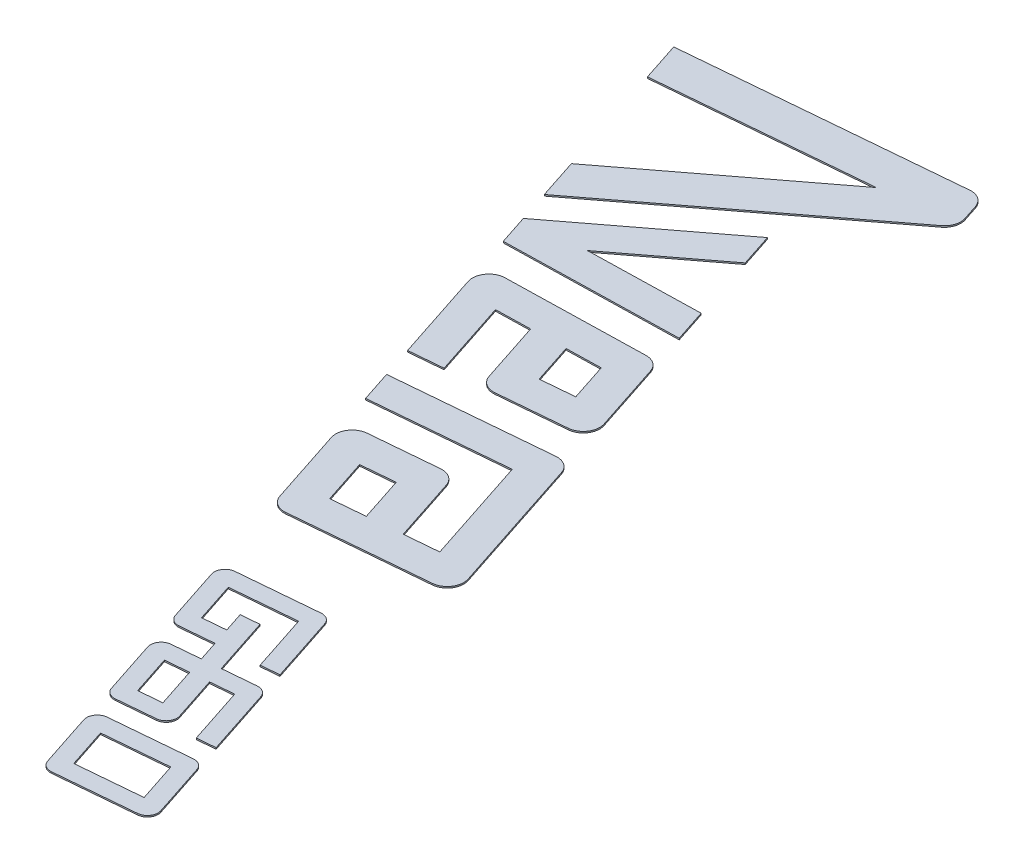
SolidWorks part; units mm, degrees
ref_plane "Front Plane" through (0, 0, 0) normal (0, 0, 1) x (1, 0, 0)
ref_plane "Top Plane" through (0, 0, 0) normal (0, 1, 0) x (1, 0, 0)
ref_plane "Right Plane" through (0, 0, 0) normal (1, 0, 0) x (0, 0, -1)
sketch "Sketch1" plane through (0, 0, 0) normal (0, 1, 0) x (1, 0, 0)
  line L0 (6.2636, 13.3847) -> (6.9802, 11.1991) construction
  line L2 (6.9802, 11.1991) -> (16.6844, 18.5822)
  line L4 (6.9802, 11.1991) -> (7.6656, 9.1086)
  line L5 (19.6969, 9.3941) -> (20.4135, 7.2086) construction
  line L6 (7.6656, 9.1086) -> (19.6969, 9.3941)
  line L10 (7.6656, 9.1086) -> (8.3822, 6.9231) construction
  line L11 (19.5596, 7.1883) -> (9.93, 6.9598)
  line L15 (19.6969, 9.3941) -> (18.9484, 11.677)
  line L20 (11.1641, 11.4923) -> (18.9484, 11.677)
  line L21 (11.1641, 11.4923) -> (17.4428, 16.2692)
  line L26 (11.5324, 4.6972) -> (13.2849, -0.6478)
  line L27 (17.4428, 16.2692) -> (16.6844, 18.5822)
  line L32 (13.0803, 4.7339) -> (11.5324, 4.6972)
  line L39 (5.3404, 16.2005) -> (2.7423, 24.1247) construction
  line L45 (17.2762, 2.0125) -> (16.3584, 4.8117)
  line L46 (13.2849, -0.6478) -> (10.9324, -0.855)
  line L56 (13.0821, -7.4116) -> (20.1616, -6.7881) construction
  line L58 (6.2636, 13.3847) -> (5.3404, 16.2005)
  line L59 (17.4595, 25.4208) -> (5.3404, 16.2005)
  line L60 (13.0821, -7.4116) -> (15.5745, -15.0134) construction
  line L61 (15.5745, -15.0134) -> (27.3591, -13.9756) construction
  line L62 (20.4135, 7.2086) -> (8.3822, 6.9231) construction
  line L64 (20.4135, 7.2086) -> (22.717, 0.1828) construction
  line L65 (8.8645, 5.4519) -> (10.9324, -0.855)
  line L66 (18.7602, 4.8687) -> (16.3584, 4.8117)
  line L68 (20.6796, 6.3969) -> (22.2656, 1.5595)
  line L69 (14.2003, 3.9425) -> (15.3531, 0.4267)
  line L71 (18.7602, 4.8687) -> (19.6287, 2.2197)
  line L72 (19.6287, 2.2197) -> (17.2762, 2.0125)
  line L73 (21.2738, 0.0557) -> (16.5467, -0.3606)
  line L74 (22.717, 0.1828) -> (10.9324, -0.855) construction
  line L75 (18.7602, 4.8687) -> (8.4367, 4.6237) construction
  line L76 (11.6489, -3.0405) -> (12.3655, -5.2261)
  line L77 (19.6287, 2.2197) -> (10.7306, 1.4361) construction
  line L78 (10.9324, -0.855) -> (11.6489, -3.0405) construction
  line L79 (11.6489, -3.0405) -> (22.5243, -2.0828)
  line L80 (12.3655, -5.2261) -> (21.7976, -4.3954)
  line L81 (23.718, -2.8701) -> (26.9077, -12.5989)
  line L82 (21.7976, -4.3954) -> (24.2708, -11.9387)
  line L83 (12.3655, -5.2261) -> (13.0821, -7.4116) construction
  line L84 (20.446, -7.6555) -> (21.9183, -12.1459)
  line L85 (14.5253, -7.2845) -> (19.2524, -6.8682)
  line L86 (13.5335, -8.7884) -> (15.2901, -14.1461)
  line L87 (16.4837, -14.9334) -> (25.9159, -14.1027)
  line L88 (21.2481, -2.7193) -> (25.1736, -14.6922) construction
  line L89 (17.1912, -12.5622) -> (19.5438, -12.355)
  line L90 (23.4336, -2.0027) -> (27.3591, -13.9756) construction
  line L91 (15.3727, -12.7223) -> (27.1574, -11.6845) construction
  line L92 (16.1704, -9.4485) -> (17.1912, -12.5622)
  line L93 (16.1704, -9.4485) -> (18.5229, -9.2414)
  line L95 (16.1704, -9.4485) -> (17.76, -14.2969) construction
  line L96 (18.5449, -9.2394) -> (19.7327, -12.8624) construction
  line L97 (21.9183, -12.1459) -> (24.2708, -11.9387)
  line L98 (1.8466, 26.8566) -> (2.7423, 24.1247)
  line L99 (16.1704, -9.4485) -> (18.5449, -9.2394) construction
  line L100 (18.5229, -9.2414) -> (19.5438, -12.355)
  line L101 (20.1616, -6.7881) -> (21.9183, -12.1459) construction
  line L102 (14.2003, 3.9425) -> (13.9342, 4.7542)
  line L103 (13.0803, 4.7339) -> (13.9342, 4.7542)
  line L104 (15.2901, -14.1461) -> (17.3311, -20.3712) construction
  line L105 (17.4595, 25.4208) -> (2.7423, 24.1247)
  line L106 (22.4342, 26.6593) -> (22.0779, 27.746)
  line L107 (22.0377, 25.3858) -> (6.2636, 13.3847)
  line L108 (18.2724, -20.2883) -> (23.8177, -19.7999)
  line L109 (20.8842, 28.5333) -> (1.8466, 26.8566)
  line L110 (21.9183, -12.1459) -> (24.4107, -19.7477) construction
  line L111 (17.6255, -21.269) -> (18.8592, -25.0318)
  line L112 (19.6376, -25.5452) -> (21.9451, -25.342)
  line L113 (24.5961, -20.3134) -> (26.1242, -24.974)
  line L114 (19.0095, -21.4782) -> (23.532, -21.0799)
  line L115 (23.532, -21.0799) -> (24.4458, -23.8669)
  line L116 (19.9233, -24.2652) -> (21.5453, -24.1224)
  line L117 (19.0095, -21.4782) -> (19.9233, -24.2652)
  line L118 (19.0446, -25.5974) -> (19.512, -27.0228) construction
  line L136 (24.4458, -23.8669) -> (24.8457, -25.0866)
  line L144 (21.2255, -32.249) -> (21.6928, -33.6744) construction
  line L145 (20.4532, -26.9399) -> (22.4125, -26.7673)
  line L146 (22.6341, -33.5915) -> (28.1794, -33.1031)
  line L147 (21.9872, -34.5723) -> (23.2209, -38.335)
  line L148 (23.9993, -38.8484) -> (29.5447, -38.3601)
  line L149 (28.9579, -33.6166) -> (30.1915, -37.3793)
  line L150 (23.3712, -34.7814) -> (27.8937, -34.3831)
  line L151 (27.8937, -34.3831) -> (28.8075, -37.1702)
  line L152 (24.285, -37.5684) -> (28.8075, -37.1702)
  line L153 (23.3712, -34.7814) -> (24.285, -37.5684)
  line L154 (21.0884, -22.7289) -> (22.3669, -22.6163)
  line L155 (21.5453, -24.1224) -> (20.6315, -21.3354) construction
  line L156 (21.5102, -20.0031) -> (23.2237, -25.2294) construction
  line L157 (19.8063, -27.9207) -> (21.04, -31.6834)
  line L158 (21.8185, -32.1968) -> (24.4633, -31.9639)
  line L159 (26.777, -26.965) -> (28.3051, -31.6256)
  line L160 (21.1904, -28.1298) -> (22.8123, -27.987)
  line L161 (25.7129, -27.7315) -> (26.6266, -30.5186)
  line L162 (22.1042, -30.9168) -> (23.7261, -30.774)
  line L163 (21.1904, -28.1298) -> (22.1042, -30.9168)
  line L164 (26.6266, -30.5186) -> (27.0265, -31.7382)
  line L165 (22.8123, -27.987) -> (23.7261, -30.774)
  line L166 (24.0909, -27.8744) -> (25.1102, -30.9831)
  line L167 (27.0265, -31.7382) -> (28.3051, -31.6256)
  line L168 (24.0909, -27.8744) -> (25.7129, -27.7315)
  line L169 (23.691, -26.6547) -> (22.6649, -23.5252)
  line L171 (21.3864, -23.6378) -> (21.5453, -24.1224)
  line L172 (22.3669, -22.6163) -> (22.6649, -23.5252)
  line L173 (19.9233, -24.2652) -> (24.4458, -23.8669) construction
  line L174 (24.8457, -25.0866) -> (26.1242, -24.974)
  line L175 (19.0446, -25.5974) -> (26.1242, -24.974) construction
  line L176 (21.9451, -25.342) -> (22.4125, -26.7673)
  line L177 (23.691, -26.6547) -> (25.9985, -26.4515)
  line L178 (21.0884, -22.7289) -> (21.3864, -23.6378)
  line L179 (17.3311, -20.3712) -> (19.0446, -25.5974) construction
  line L180 (17.3311, -20.3712) -> (24.4107, -19.7477) construction
  line L181 (24.4107, -19.7477) -> (26.1242, -24.974) construction
  arc A0 (14.5253, -7.2845) -> (13.5335, -8.7884) centre (14.6262, -8.4301) ccw
  arc A1 (16.4837, -14.9334) -> (15.2901, -14.1461) centre (16.3829, -13.7878) cw
  arc A2 (22.0377, 25.3858) -> (22.4342, 26.6593) centre (21.3414, 26.301) ccw
  arc A3 (22.0779, 27.746) -> (20.8842, 28.5333) centre (20.9851, 27.3877) ccw
  arc A5 (9.93, 6.9598) -> (8.8645, 5.4519) centre (9.9573, 5.8101) ccw
  arc A6 (19.5596, 7.1883) -> (20.6796, 6.3969) centre (19.5868, 6.0387) cw
  arc A7 (25.9159, -14.1027) -> (26.9077, -12.5989) centre (25.815, -12.9572) ccw
  arc A8 (23.718, -2.8701) -> (22.5243, -2.0828) centre (22.6252, -3.2284) ccw
  arc A9 (16.5467, -0.3606) -> (15.3531, 0.4267) centre (16.4458, 0.785) cw
  arc A10 (21.2738, 0.0557) -> (22.2656, 1.5595) centre (21.1729, 1.2013) ccw
  arc A11 (19.2524, -6.8682) -> (20.446, -7.6555) centre (19.3533, -8.0138) cw
  arc A12 (24.4633, -31.9639) -> (25.1102, -30.9831) centre (24.3975, -31.2168) ccw
  arc A13 (28.9579, -33.6166) -> (28.1794, -33.1031) centre (28.2452, -33.8503) ccw
  arc A14 (30.1915, -37.3793) -> (29.5447, -38.3601) centre (29.4789, -37.613) cw
  arc A15 (23.9993, -38.8484) -> (23.2209, -38.335) centre (23.9336, -38.1013) cw
  arc A16 (21.9872, -34.5723) -> (22.6341, -33.5915) centre (22.6999, -34.3386) cw
  arc A17 (21.8185, -32.1968) -> (21.04, -31.6834) centre (21.7527, -31.4497) cw
  arc A18 (19.8063, -27.9207) -> (20.4532, -26.9399) centre (20.519, -27.687) cw
  arc A19 (25.9985, -26.4515) -> (26.777, -26.965) centre (26.0643, -27.1986) cw
  arc A20 (19.6376, -25.5452) -> (18.8592, -25.0318) centre (19.5718, -24.7981) cw
  arc A21 (17.6255, -21.269) -> (18.2724, -20.2883) centre (18.3382, -21.0354) cw
  arc A22 (23.8177, -19.7999) -> (24.5961, -20.3134) centre (23.8835, -20.547) cw
  point P117 (20.2316, -20.1157)
  point P120 (21.9451, -25.342)
  point P121 (21.5102, -20.0031)
  point P122 (23.2237, -25.2294)
  point P123 (22.4125, -26.7673)
  point P124 (24.126, -31.9936)
  point P125 (23.691, -26.6547)
  point P126 (25.4046, -31.881)
  point P133 (25.4046, -31.881)
  point P136 (28.7724, -33.0509)
  point P139 (30.4859, -38.2772)
  point P152 (26.5915, -26.3993)
  dimension "D1" = 1.15
  dimension "D2" = 1.15
  dimension "D7" = 0.75
  dimension "D3" = 5.5
  dimension "D4" = 1.25
  dimension "D5" = 5.5
  dimension "D6" = 5.5
extrude "Boss-Extrude1" add sketch "Sketch1" along normal blind 0.1
